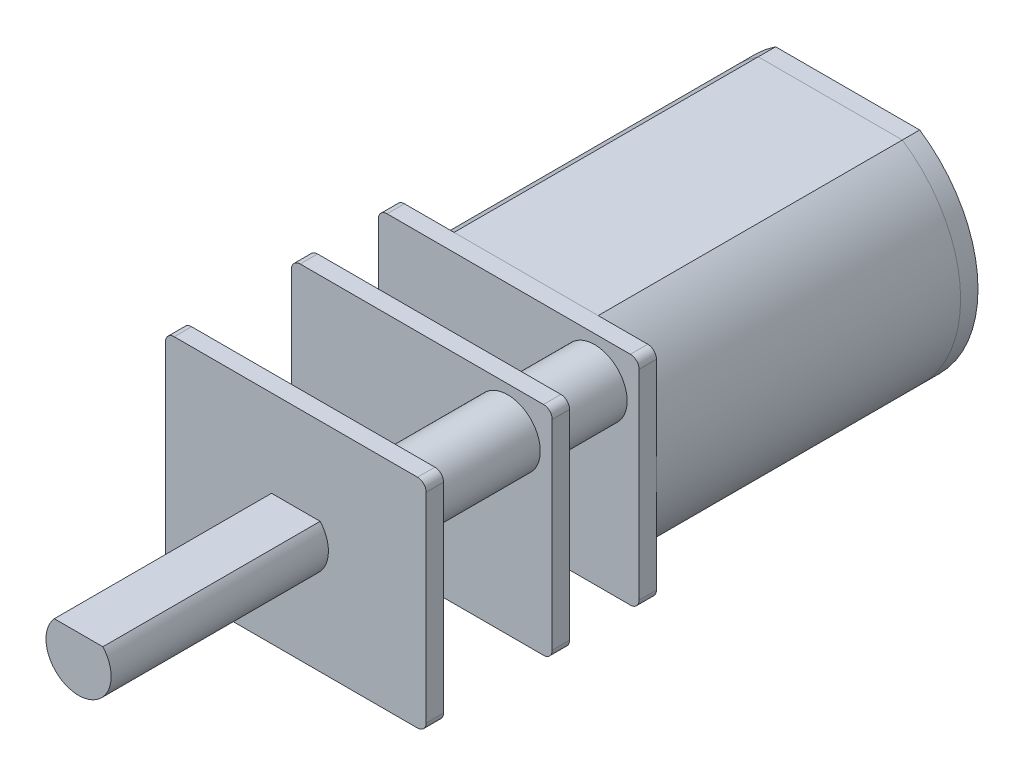
SolidWorks part; units mm, degrees
ref_plane "Front" through (0, 0, 0) normal (0, 0, 1) x (1, 0, 0)
ref_plane "Top" through (0, 0, 0) normal (0, 1, 0) x (1, 0, 0)
ref_plane "Right" through (0, 0, 0) normal (1, 0, 0) x (0, 0, -1)
sketch "草圖1" plane through (0, 0, 0) normal (0, 0, 1) x (1, 0, 0)
  line L0 (-6, 0) -> (6, 0) construction
  line L1 (-3.3166, -5) -> (3.3166, -5)
  line L2 (-3.3166, -5) -> (-3.3166, 5) construction
  line L3 (-3.3166, 5) -> (3.3166, 5)
  line L4 (3.3166, -5) -> (3.3166, 5) construction
  line L5 (-3.3166, -5) -> (3.3166, 5) construction
  line L6 (-3.3166, 5) -> (3.3166, -5) construction
  arc A0 (3.3166, 5) -> (3.3166, -5) centre (0, 0) cw
  arc A1 (-3.3166, 5) -> (-3.3166, -5) centre (0, 0) ccw
  point P0 (0, 0)
  dimension "D2" = 6
  dimension "D3" = 6
  dimension "D4" = 12
  dimension "D1" = 10
extrude "填料-伸長1" add sketch "草圖1" along normal blind 14
sketch "草圖8" plane through (0, 0, 0) normal (0, 0, -1) x (-1, 0, 0)
  line L2 (-3.3166, -5) -> (3.3166, -5)
  line L3 (3.3166, 5) -> (-3.3166, 5)
  line L4 (-3.3166, -5) -> (3.3166, -5)
  line L5 (3.3166, 5) -> (-3.3166, 5)
  arc A2 (-3.3166, 5) -> (-3.3166, -5) centre (0, 0) ccw
  arc A3 (3.3166, -5) -> (3.3166, 5) centre (0, 0) ccw
  arc A4 (-3.3166, 5) -> (-3.3166, -5) centre (0, 0) ccw
  arc A5 (3.3166, -5) -> (3.3166, 5) centre (0, 0) ccw
  dimension "D1" = 0
extrude "填料-伸長8" add sketch "草圖8" along normal blind 0.8 separate body
sketch "草圖2" plane through (0, 0, 0) normal (0, 0, -1) x (-1, 0, 0)
  circle A0 centre (0, 0) radius 2.5
  dimension "D1" = 5
extrude "填料-伸長2" add sketch "草圖2" along normal blind 1.5
sketch "草圖3" plane through (0, 0, 14) normal (0, 0, 1) x (1, 0, 0)
  line L1 (-5.6, 5) -> (5.6, 5)
  line L2 (-6, 4.6) -> (-6, -4.6)
  line L3 (-5.6, -5) -> (5.6, -5)
  line L4 (6, 4.6) -> (6, -4.6)
  line L5 (-6, 5) -> (6, -5) construction
  line L6 (-6, -5) -> (6, 5) construction
  arc A0 (-6, -4.6) -> (-5.6, -5) centre (-5.6, -4.6) ccw
  arc A1 (5.6, -5) -> (6, -4.6) centre (5.6, -4.6) ccw
  arc A2 (5.6, 5) -> (6, 4.6) centre (5.6, 4.6) cw
  arc A3 (-5.6, 5) -> (-6, 4.6) centre (-5.6, 4.6) ccw
  point P0 (0, 0)
  dimension "D3" = 0.4
  dimension "D1" = 10
  dimension "D2" = 12
extrude "填料-伸長3" add sketch "草圖3" along normal blind 0.8 separate body
sketch "草圖4" plane through (0, 0, 14.8) normal (0, 0, 1) x (1, 0, 0)
  line L4 (-5.6, -5) -> (5.6, -5)
  line L5 (6, -4.6) -> (6, 4.6)
  line L6 (5.6, 5) -> (-5.6, 5)
  line L7 (-6, 4.6) -> (-6, -4.6)
  line L8 (-5.6, -5) -> (5.6, -5)
  line L9 (6, -4.6) -> (6, 4.6)
  line L10 (5.6, 5) -> (-5.6, 5)
  line L11 (-6, 4.6) -> (-6, -4.6)
  arc A4 (-6, -4.6) -> (-5.6, -5) centre (-5.6, -4.6) ccw
  arc A5 (5.6, -5) -> (6, -4.6) centre (5.6, -4.6) ccw
  arc A6 (6, 4.6) -> (5.6, 5) centre (5.6, 4.6) ccw
  arc A7 (-5.6, 5) -> (-6, 4.6) centre (-5.6, 4.6) ccw
  arc A8 (-6, -4.6) -> (-5.6, -5) centre (-5.6, -4.6) ccw
  arc A9 (5.6, -5) -> (6, -4.6) centre (5.6, -4.6) ccw
  arc A10 (6, 4.6) -> (5.6, 5) centre (5.6, 4.6) ccw
  arc A11 (-5.6, 5) -> (-6, 4.6) centre (-5.6, 4.6) ccw
  dimension "D1" = 0
extrude "填料-伸長4" add sketch "草圖4" along normal blind 0.8 from offset 3.2 separate body
sketch "草圖5" plane through (0, 0, 18.8) normal (0, 0, 1) x (1, 0, 0)
  line L4 (-5.6, -5) -> (5.6, -5)
  line L5 (6, -4.6) -> (6, 4.6)
  line L6 (5.6, 5) -> (-5.6, 5)
  line L7 (-6, 4.6) -> (-6, -4.6)
  line L8 (-5.6, -5) -> (5.6, -5)
  line L9 (6, -4.6) -> (6, 4.6)
  line L10 (5.6, 5) -> (-5.6, 5)
  line L11 (-6, 4.6) -> (-6, -4.6)
  arc A4 (-6, -4.6) -> (-5.6, -5) centre (-5.6, -4.6) ccw
  arc A5 (5.6, -5) -> (6, -4.6) centre (5.6, -4.6) ccw
  arc A6 (6, 4.6) -> (5.6, 5) centre (5.6, 4.6) ccw
  arc A7 (-5.6, 5) -> (-6, 4.6) centre (-5.6, 4.6) ccw
  arc A8 (-6, -4.6) -> (-5.6, -5) centre (-5.6, -4.6) ccw
  arc A9 (5.6, -5) -> (6, -4.6) centre (5.6, -4.6) ccw
  arc A10 (6, 4.6) -> (5.6, 5) centre (5.6, 4.6) ccw
  arc A11 (-5.6, 5) -> (-6, 4.6) centre (-5.6, 4.6) ccw
  dimension "D1" = 0
extrude "填料-伸長5" add sketch "草圖5" along normal blind 0.8 from offset 5 separate body
sketch "草圖6" plane through (0, 0, 14.8) normal (0, 0, 1) x (1, 0, 0)
  line L0 (-3.9512, -3.064) -> (3.9512, 3.064) construction
  circle A0 centre (3.9512, 3.064) radius 1.5
  circle A1 centre (-3.9512, -3.064) radius 1.5
  dimension "D1" = 3
  dimension "D2" = 3
  dimension "D3" = 10
extrude "填料-伸長6" add sketch "草圖6" along normal up to surface (9.8 mm away) up to face at (0, 0, 24.6)
sketch "草圖7" plane through (0, 0, 24.6) normal (0, 0, 1) x (1, 0, 0)
  line L0 (-1.118, 1) -> (1.118, 1)
  arc A0 (-1.118, 1) -> (1.118, 1) centre (0, 0) ccw
  dimension "D1" = 3
  dimension "D2" = 1
extrude "填料-伸長7" add sketch "草圖7" along normal blind 10 separate body
